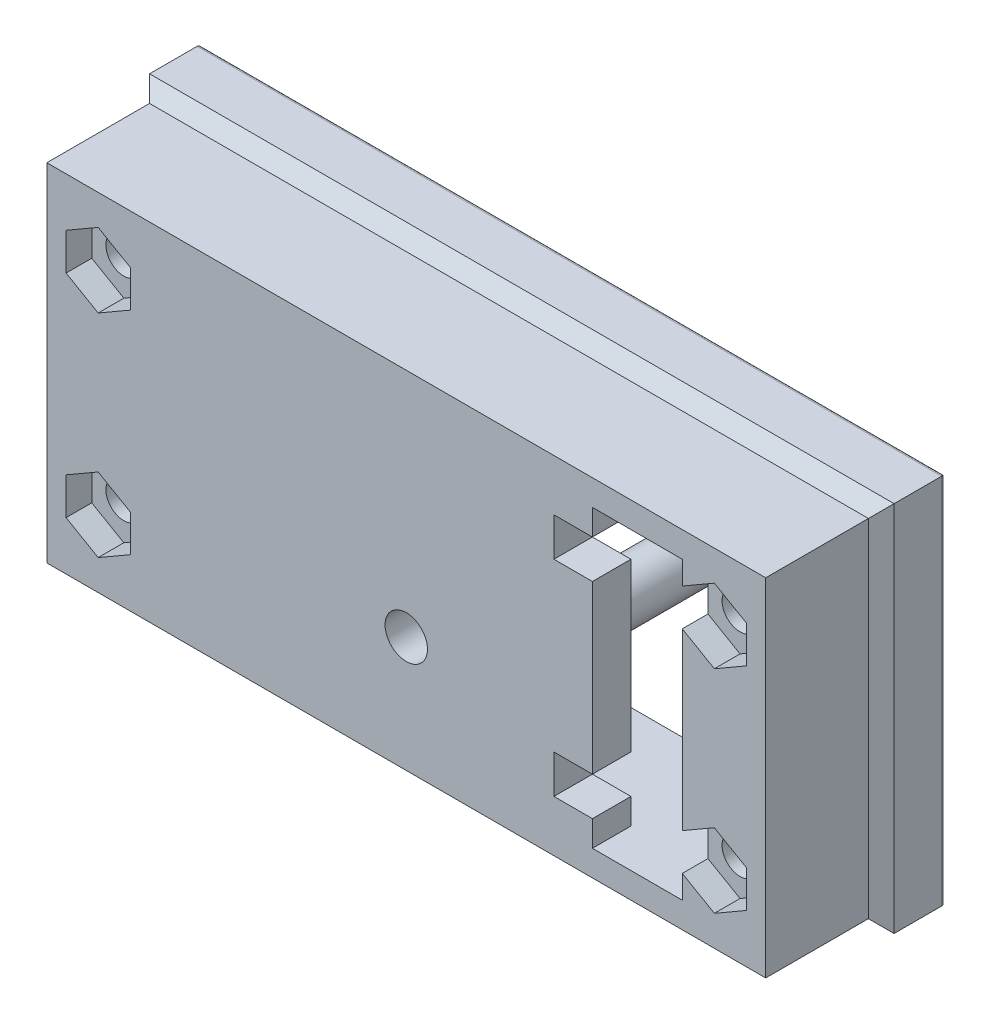
SolidWorks part; units mm, degrees
ref_plane "Front Plane" through (0, 0, 0) normal (0, 0, 1) x (1, 0, 0)
ref_plane "Top Plane" through (0, 0, 0) normal (0, 1, 0) x (1, 0, 0)
ref_plane "Right Plane" through (0, 0, 0) normal (1, 0, 0) x (0, 0, -1)
sketch "Sketch1" plane through (0, 0, 0) normal (0, 0, 1) x (1, 0, 0)
  line L1 (28, -13.5) -> (-28, -13.5)
  line L2 (28, -13.5) -> (28, 13.5)
  line L3 (28, 13.5) -> (-28, 13.5)
  line L4 (-28, -13.5) -> (-28, 13.5)
  line L5 (28, -13.5) -> (-28, 13.5) construction
  line L6 (28, 13.5) -> (-28, -13.5) construction
  line L7 (26, -11.5) -> (-26, -11.5)
  line L8 (26, -11.5) -> (26, 11.5)
  line L9 (26, 11.5) -> (-26, 11.5)
  line L10 (-26, -11.5) -> (-26, 11.5)
  line L11 (26, -11.5) -> (-26, 11.5) construction
  line L12 (26, 11.5) -> (-26, -11.5) construction
  point P0 (0, 0)
  point P6 (0, 0)
  dimension "D1" = 52
  dimension "D2" = 23
  dimension "D3" = 2
  dimension "D4" = 2
extrude "Boss-Extrude1" add sketch "Sketch1" along normal blind 8
sketch "Sketch2" plane through (0, 0, 8) normal (0, 0, 1) x (1, 0, 0)
  line L1 (28, -13.5) -> (-28, -13.5)
  line L2 (28, -13.5) -> (28, 13.5)
  line L3 (28, 13.5) -> (-28, 13.5)
  line L4 (-28, -13.5) -> (-28, 13.5)
  line L5 (28, -13.5) -> (-28, 13.5) construction
  line L6 (28, 13.5) -> (-28, -13.5) construction
  point P0 (0, 0)
extrude "Boss-Extrude2" add sketch "Sketch2" along normal blind 3
sketch "Sketch4" plane through (0, 0, 8) normal (0, 0, -1) x (-1, 0, 0)
  line L0 (26, -11.5) -> (-26, -11.5) construction
  line L1 (-21.5, 11.5) -> (-14.5, 11.5)
  line L2 (-21.5, 11.5) -> (-21.5, -11.5)
  line L3 (-21.5, -11.5) -> (-14.5, -11.5)
  line L4 (-14.5, 11.5) -> (-14.5, -11.5)
  line L5 (26, 11.5) -> (26, -11.5) construction
  line L6 (-26, 11.5) -> (26, 11.5) construction
  dimension "D1" = 7
  dimension "D2" = 40.5
extrude "Cut-Extrude1" cut sketch "Sketch4" against normal blind 3
sketch "Sketch5" plane through (0, 0, 8) normal (0, 0, -1) x (-1, 0, 0)
  circle A0 centre (-10, 0) radius 2
  dimension "D1" = 4
  dimension "D2" = 10
extrude "Boss-Extrude3" add sketch "Sketch5" along normal blind 9.7
fillet "Fillet1" radius 2 1 edges at (12, 0, 8)
sketch "Sketch6" plane through (0, 0, 8) normal (0, 0, -1) x (-1, 0, 0)
  line L0 (24, 8.25) -> (24, -8.25) construction
  line L1 (26, 11.5) -> (26, -11.5) construction
  line L2 (-24, 8.25) -> (-24, -8.25) construction
  line L3 (-26, -11.5) -> (-26, 11.5) construction
  line L4 (-28, -13.5) -> (-28, 13.5) construction
  circle A0 centre (24, 8.25) radius 1.4
  circle A1 centre (24, -8.25) radius 1.4
  circle A2 centre (-24, 8.25) radius 1.4
  circle A3 centre (-24, -8.25) radius 1.4
  point P4 (24, 0)
  point P6 (0, 0)
  point P17 (-24, 0)
  dimension "D2" = 2.8
  dimension "D3" = 2.8
  dimension "D4" = 2
  dimension "D5" = 16.5
  dimension "D6" = 4
  dimension "D1" = 16.5
extrude "Cut-Extrude2" cut sketch "Sketch6" against normal blind 10
sketch "Sketch8" plane through (0, 0, 11) normal (0, 0, 1) x (1, 0, 0)
  line L1 (-26.5, 9.6934) -> (-26.5, 6.8066)
  line L2 (-26.5, 6.8066) -> (-24, 5.3632)
  line L3 (-24, 5.3632) -> (-21.5, 6.8066)
  line L4 (-21.5, 6.8066) -> (-21.5, 9.6934)
  line L5 (-21.5, 9.6934) -> (-24, 11.1368)
  line L6 (-24, 11.1368) -> (-26.5, 9.6934)
  line L7 (-24, -5.3632) -> (-26.5, -6.8066)
  line L8 (-26.5, -6.8066) -> (-26.5, -9.6934)
  line L9 (-26.5, -9.6934) -> (-24, -11.1368)
  line L10 (-24, -11.1368) -> (-21.5, -9.6934)
  line L11 (-21.5, -9.6934) -> (-21.5, -6.8066)
  line L12 (-21.5, -6.8066) -> (-24, -5.3632)
  line L13 (24, 11.1368) -> (21.5, 9.6934)
  line L14 (-28, 13.5) -> (-28, -13.5) construction
  line L15 (21.5, 9.6934) -> (21.5, 6.8066)
  line L16 (21.5, 6.8066) -> (24, 5.3632)
  line L17 (24, 5.3632) -> (26.5, 6.8066)
  line L18 (26.5, 6.8066) -> (26.5, 9.6934)
  line L19 (26.5, 9.6934) -> (24, 11.1368)
  line L20 (24, -5.3632) -> (21.5, -6.8066)
  line L21 (21.5, -6.8066) -> (21.5, -9.6934)
  line L22 (21.5, -9.6934) -> (24, -11.1368)
  line L23 (24, -11.1368) -> (26.5, -9.6934)
  line L24 (26.5, -9.6934) -> (26.5, -6.8066)
  line L25 (26.5, -6.8066) -> (24, -5.3632)
  circle A0 centre (-24, 8.25) radius 2.5 construction
  circle A1 centre (-24, -8.25) radius 2.5 construction
  circle A2 centre (24, 8.25) radius 2.5 construction
  circle A3 centre (24, -8.25) radius 2.5 construction
  dimension "D1" = 5
  dimension "D2" = 5
extrude "Cut-Extrude3" cut sketch "Sketch8" against normal blind 2
sketch "Sketch10" plane through (0, 0, 8) normal (0, 0, -1) x (-1, 0, 0)
  line L1 (26, 11.5) -> (17.3098, 11.5)
  line L2 (26, 11.5) -> (26, 3.9581)
  line L3 (26, 3.9581) -> (17.3098, 3.9581)
  line L4 (17.3098, 11.5) -> (17.3098, 3.9581)
  line L5 (26, -11.5) -> (16.8129, -11.5)
  line L6 (26, -11.5) -> (26, -4.0462)
  line L7 (26, -4.0462) -> (16.8129, -4.0462)
  line L8 (16.8129, -11.5) -> (16.8129, -4.0462)
  line L9 (-26, 11.5) -> (-20.6838, 11.5)
  line L10 (-26, 11.5) -> (-26, 4.9094)
  line L11 (-26, 4.9094) -> (-20.6838, 4.9094)
  line L12 (-20.6838, 11.5) -> (-20.6838, 4.9094)
  line L13 (-26, -11.5) -> (-20.0802, -11.5)
  line L14 (-26, -11.5) -> (-26, -4.507)
  line L15 (-26, -4.507) -> (-20.0802, -4.507)
  line L16 (-20.0802, -11.5) -> (-20.0802, -4.507)
  circle A0 centre (24, 8.25) radius 1.4
  circle A1 centre (24, -8.25) radius 1.4
  circle A2 centre (24, -8.25) radius 2.4
  circle A3 centre (24, 8.25) radius 2.4
  circle A4 centre (24, 8.25) radius 1.4 construction
  circle A5 centre (-24, 8.25) radius 1.4
  circle A6 centre (-24, 8.25) radius 2.4
  circle A7 centre (-24, -8.25) radius 1.4
  circle A8 centre (-24, -8.25) radius 2.4
  circle M13 centre (24, 8.25) radius 1.4
  circle M14 centre (24, -8.25) radius 1.4
  dimension "D1" = 1
  dimension "D2" = 1
sketch "Sketch11" plane through (0, 0, 8) normal (0, 0, -1) x (-1, 0, 0)
  line L0 (-14.5, -11.5) -> (-14.5, 11.5) construction
  line L1 (-14.5, 9.5) -> (-11.5, 9.5)
  line L2 (-14.5, 9.5) -> (-14.5, 6.5)
  line L3 (-14.5, 6.5) -> (-11.5, 6.5)
  line L4 (-11.5, 9.5) -> (-11.5, 6.5)
  line L5 (-26, 11.5) -> (26, 11.5) construction
  line L6 (-14.5, -6.5) -> (-11.5, -6.5)
  line L7 (-14.5, -6.5) -> (-14.5, -9.5)
  line L8 (-14.5, -9.5) -> (-11.5, -9.5)
  line L9 (-11.5, -6.5) -> (-11.5, -9.5)
  line L10 (26, -11.5) -> (-14.5, -11.5) construction
  line L13 (28, -13.5) -> (-28, -13.5) construction
  circle A0 centre (0, -4.5) radius 1.65
  dimension "D1" = 3.3
  dimension "D6" = 9
  dimension "D2" = 3
  dimension "D3" = 3
  dimension "D4" = 2
  dimension "D5" = 2
extrude "Cut-Extrude4" cut sketch "Sketch11" against normal blind 10
extrude "Boss-Extrude5" add sketch "Sketch10" along normal blind 10 contours L2 A3 M13 | L6 A2 M14 region at (-25.9349, 8.25, 8) region at (-21.6651, -8.25, 8)
extrude "Boss-Extrude6" add sketch "Sketch10<5>" along normal blind 12.5 contours L10 A6 A5 | L14 A8 A7 region at (23.326, 10.4855, 8) region at (25.9349, -8.25, 8)
sketch "Sketch10<5>" plane through (0, 0, 8) normal (0, 0, -1) x (-1, 0, 0) same geometry as "Sketch10"
sketch "Sketch12" plane through (0, 0, 0) normal (0, 0, -1) x (-1, 0, 0)
  line L1 (-28, 13.5) -> (28, 13.5)
  line L2 (-28, 13.5) -> (-28, -13.5)
  line L3 (-28, -13.5) -> (28, -13.5)
  line L4 (28, 13.5) -> (28, -13.5)
  line L5 (-29, 14.5) -> (29, 14.5)
  line L6 (-29, 14.5) -> (-29, -14.5)
  line L7 (-29, -14.5) -> (29, -14.5)
  line L8 (29, 14.5) -> (29, -14.5)
  dimension "D1" = 1
  dimension "D2" = 1
  dimension "D3" = 1
  dimension "D4" = 1
extrude "Boss-Extrude7" add sketch "Sketch12" along normal blind 2 and the other way blind 2
sketch "Sketch14" plane through (0, 0, 8) normal (0, 0, -1) x (-1, 0, 0)
  line L0 (-14.5, -6.5) -> (-14.5, 6.5) construction
  line L1 (0, -1.3246) -> (-2.75, -2.9123)
  line L2 (-2.75, -2.9123) -> (-2.75, -6.0877)
  line L3 (-2.75, -6.0877) -> (0, -7.6754)
  line L4 (0, -7.6754) -> (2.75, -6.0877)
  line L5 (2.75, -6.0877) -> (2.75, -2.9123)
  line L6 (2.75, -2.9123) -> (0, -1.3246)
  line L7 (0, 0.9848) -> (-4.75, -1.7576)
  line L8 (-4.75, -1.7576) -> (-4.75, -7.2424)
  line L9 (-4.75, -7.2424) -> (0, -9.9848)
  line L10 (0, -9.9848) -> (4.75, -7.2424)
  line L11 (4.75, -7.2424) -> (4.75, -1.7576)
  line L12 (4.75, -1.7576) -> (0, 0.9848)
  circle A0 centre (0, -4.5) radius 2.75 construction
  circle A1 centre (0, -4.5) radius 4.75 construction
  dimension "D1" = 5.5
  dimension "D2" = 2
extrude "Boss-Extrude8" add sketch "Sketch14" along normal blind 3
fillet "Fillet2" radius 0.3 8 edges at (-28, 0, -2) (0, 13.5, -2) (28, 0, -2) (0, -13.5, -2) (0, 14.5, -2) (-29, 0, -2) (0, -14.5, -2) (29, 0, -2)
fillet "Fillet3" radius 0.3 13 edges at (8, 0, -1.7) (-21.6, -8.25, -2) (-26, -8.25, -2) (-25.4, -8.25, -2) (-21.6, 8.25, -2) (-26, 8.25, -2) (-25.4, 8.25, -2) (21.6, 8.25, -4.5) (26, 8.25, -4.5) (22.6, 8.25, -4.5) (21.6, -8.25, -4.5) (26, -8.25, -4.5) (22.6, -8.25, -4.5)
chamfer "Chamfer1" distance 1 angle 45 4 edges at (0, -13.5, 2) (28, 0, 2) (-28, 0, 2) (0, 13.5, 2)
